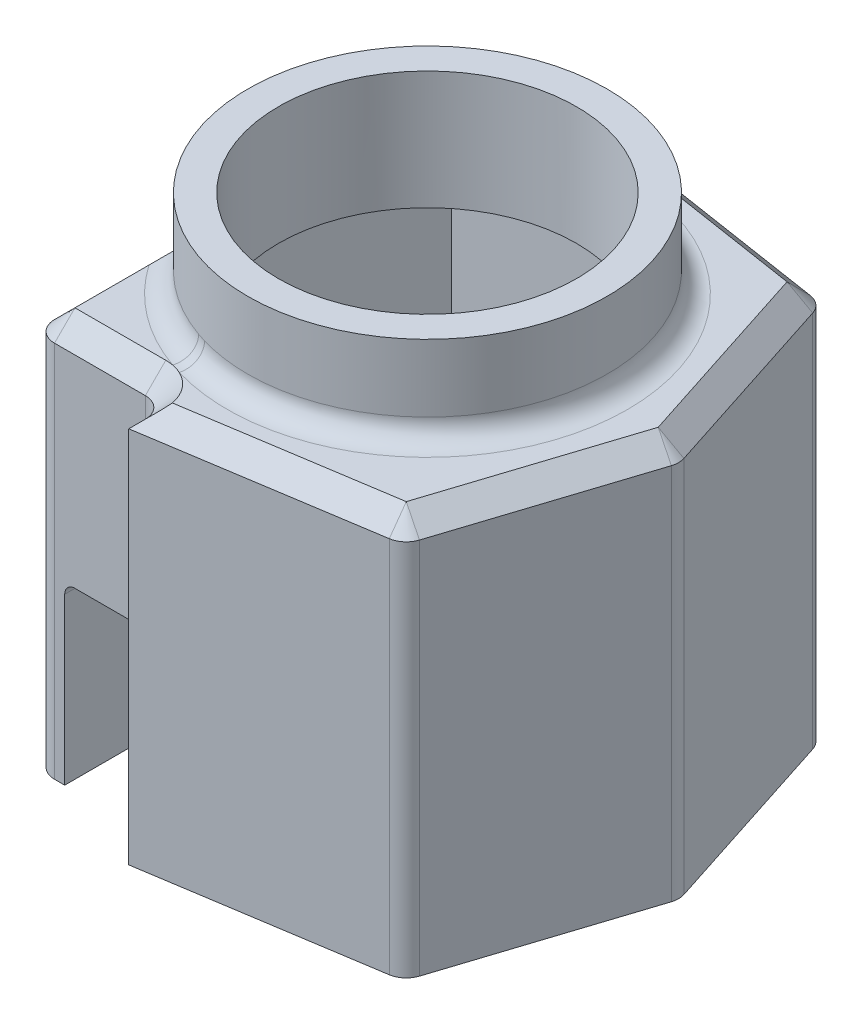
SolidWorks part; units mm, degrees
ref_plane "Front Plane" through (0, 0, 0) normal (0, 0, 1) x (1, 0, 0)
ref_plane "Top Plane" through (0, 0, 0) normal (0, 1, 0) x (1, 0, 0)
ref_plane "Right Plane" through (0, 0, 0) normal (1, 0, 0) x (0, 0, -1)
sketch "Sketch1" plane through (0, 0, 0) normal (0, 1, 0) x (1, 0, 0)
  line L1 (-14.9, -17.235) -> (14.9, -17.235)
  line L2 (-14.9, -17.235) -> (-14.9, 17.235)
  line L3 (-14.9, 17.235) -> (14.9, 17.235)
  line L4 (14.9, -17.235) -> (14.9, 17.235)
  line L5 (-14.9, -17.235) -> (14.9, 17.235) construction
  line L6 (-14.9, 17.235) -> (14.9, -17.235) construction
  point P0 (0, 0)
  dimension "D1" = 34.47
  dimension "D2" = 29.8
extrude "Boss-Extrude1" add sketch "Sketch1" along normal blind 33.8
sketch "Sketch2" plane through (0, 33.8, 0) normal (0, 1, 0) x (1, 0, 0)
  circle A0 centre (0, 0) radius 14.4
  dimension "D1" = 28.8
extrude "Boss-Extrude2" add sketch "Sketch2" along normal blind 11.8
sketch "Sketch3" plane through (0, 0, 17.235) normal (0, 0, 1) x (1, 0, 0)
  line L1 (-14.9, 0) -> (-5.4, 0)
  line L2 (-14.9, 0) -> (-14.9, 15)
  line L3 (-14.9, 15) -> (-5.4, 15)
  line L4 (-5.4, 0) -> (-5.4, 15)
  dimension "D1" = 15
  dimension "D2" = 9.5
extrude "Boss-Extrude3" add sketch "Sketch3" against normal offset from surface (54.47 mm away) 10 from offset 10 up to face at (0, 16.9, -17.235) offset beyond the face yes
sketch "Sketch4" plane through (0, 45.6, 0) normal (0, 1, 0) x (1, 0, 0)
  circle A1 centre (0, 0) radius 17.6
  circle A2 centre (0, 0) radius 14.6
  circle A3 centre (0, 0) radius 14.6
  dimension "D1" = 0.2
  dimension "D2" = 3
extrude "Boss-Extrude4" add sketch "Sketch4" against normal offset from surface (11.6 mm away) 0.2 separate body up to face at (0, 33.8, 14.4)
sketch "Sketch5" plane through (0, 34, 0) normal (0, -1, 0) x (1, 0, 0)
  line L4 (-18.1, -20.435) -> (18.1, -20.435)
  line L5 (18.1, -20.435) -> (18.1, 20.435)
  line L6 (18.1, 20.435) -> (-18.1, 20.435)
  line L7 (-18.1, 20.435) -> (-18.1, -20.435)
  line L8 (15.1, -17.435) -> (15.1, 17.435)
  line L9 (-15.1, -17.435) -> (15.1, -17.435)
  line L10 (-15.1, 17.435) -> (-15.1, -17.435)
  line L11 (15.1, 17.435) -> (-15.1, 17.435)
  line L12 (15.1, -17.435) -> (15.1, 17.435)
  line L13 (-15.1, -17.435) -> (15.1, -17.435)
  line L14 (-15.1, 17.435) -> (-15.1, -17.435)
  line L15 (15.1, 17.435) -> (-15.1, 17.435)
  dimension "D1" = 0.2
  dimension "D2" = 3
extrude "Boss-Extrude5" add sketch "Sketch5" along normal up to surface (34 mm away) up to face at (-2.7, 0, 0)
sketch "Sketch6" plane through (0, 0, 0) normal (0, -1, 0) x (1, 0, 0)
  line L16 (15.1, 17.435) -> (-5.2, 17.435)
  line L17 (-5.2, 17.435) -> (-5.2, 27.435)
  line L18 (-5.2, 27.435) -> (-15.1, 27.435)
  line L19 (-15.1, 27.435) -> (-15.1, -27.435)
  line L20 (-15.1, -27.435) -> (-5.2, -27.435)
  line L21 (-5.2, -27.435) -> (-5.2, -17.435)
  line L22 (-5.2, -17.435) -> (15.1, -17.435)
  line L23 (15.1, -17.435) -> (15.1, 17.435)
  line L24 (15.1, 17.435) -> (-5.2, 17.435)
  line L25 (-5.2, 17.435) -> (-5.2, 27.435)
  line L26 (-5.2, 27.435) -> (-15.1, 27.435)
  line L27 (-15.1, 27.435) -> (-15.1, -27.435)
  line L28 (-15.1, -27.435) -> (-5.2, -27.435)
  line L29 (-5.2, -27.435) -> (-5.2, -17.435)
  line L30 (-5.2, -17.435) -> (15.1, -17.435)
  line L31 (15.1, -17.435) -> (15.1, 17.435)
  dimension "D1" = 0.2
extrude "Cut-Extrude1" cut sketch "Sketch6" against normal offset from surface (15.2 mm away) 0.2 up to face at (-10.15, 15, 22.235) offset beyond the face yes
delete or keep bodies "Body-Delete/Keep 1" type delete bodies bodies 106
sketch "Sketch7" plane through (0, 34, 0) normal (0, -1, 0) x (1, 0, 0)
  line L16 (-18.1, 20.435) -> (-18.1, -20.435)
  line L17 (18.1, 20.435) -> (-18.1, 20.435)
  line L18 (18.1, -20.435) -> (18.1, 20.435)
  line L19 (-18.1, -20.435) -> (18.1, -20.435)
  line L20 (-18.1, 20.435) -> (-18.1, -20.435)
  line L21 (18.1, 20.435) -> (-18.1, 20.435)
  line L22 (18.1, -20.435) -> (18.1, 20.435)
  line L23 (-18.1, -20.435) -> (18.1, -20.435)
  circle A0 centre (0, 0) radius 14.6 construction
  circle A1 centre (0, 0) radius 14.6
  dimension "D1" = 0
extrude "Boss-Extrude6" add sketch "Sketch7" against normal blind 3
sketch "Sketch8" plane through (0, 37, 0) normal (0, 1, 0) x (1, 0, 0)
  line L0 (0, 0) -> (45.1825, 0) construction
  line L1 (18.1, 20.435) -> (24.7072, 0)
  line L2 (24.7072, 0) -> (18.1, -20.435)
  line L3 (18.1, -20.435) -> (18.1, 20.435)
  point P7 (22.4785, 0)
extrude "Boss-Extrude7" add sketch "Sketch8" against normal up to surface (37 mm away) up to face at (5.7, 0, 0)
sketch "Sketch9" plane through (0, 37, 0) normal (0, 1, 0) x (1, 0, 0)
  line L0 (-5.2, 20.435) -> (-5.2, 24.0622)
  line L1 (-5.2, 24.0622) -> (18.1, 20.435)
  line L2 (18.1, 20.435) -> (-5.2, 20.435)
  line L3 (0, 0) -> (41.759, 0) construction
  line L4 (18.1, -20.435) -> (-5.2, -20.435)
  line L5 (-5.2, -24.0622) -> (18.1, -20.435)
  line L6 (-5.2, -20.435) -> (-5.2, -24.0622)
  line M3 (18.1, 20.435) -> (-18.1, 20.435)
  line M5 (-18.1, -20.435) -> (18.1, -20.435)
extrude "Boss-Extrude8" add sketch "Sketch9" against normal up to surface (37 mm away) contours L1 L0 M3 | L6 L5 M5 region at (2.5667, 37, -21.6441) region at (2.5667, 37, 21.6441) up to face at (-16.6, 0, 0)
fillet "Fillet1" radius 2 7 edges at (-18.1, 18.5, 20.435) (-18.1, 18.5, -20.435) (18.1, 18.5, 20.435) (18.1, 18.5, -20.435) (24.7072, 18.5, 0) (-5.2, 26.1, 20.435) (-5.2, 26.1, -20.435)
fillet "Fillet2" radius 1 4 edges at (-15.1, 15.2, 18.935) (-5.2, 15.2, 19.935) (-15.1, 15.2, -18.935) (-5.2, 15.2, -19.935)
chamfer "Chamfer4" distance 2 angle 45 14 edges at (-5.7858, 37, 21.0208) (-5.7858, 37, -21.0208) (-11.65, 37, 20.435) (-11.65, 37, -20.435) (-17.5142, 37, 19.8492) (-17.5142, 37, -19.8492) (-18.1, 37, 0) (5.8417, 37, 22.3433) (17.8738, 37, 20.1698) (21.4935, 37, 9.9394) (24.6053, 37, 0) (21.4935, 37, -9.9394) (17.8738, 37, -20.1698) (5.8417, 37, -22.3433)
fillet "Fillet3" radius 2 1 edges at (17.6, 37, 0)
sketch "Sketch10" plane through (0, 0, 0) normal (0, -1, 0) x (1, 0, 0)
  line L0 (-15.1, 20.435) -> (-16.1, 20.435) construction
  line L1 (-18.1, 18.435) -> (-18.1, -18.435) construction
  line L2 (-16.1, -20.435) -> (-15.1, -20.435) construction
  line L3 (-15.1, -20.435) -> (-15.1, 20.435) construction
  line L4 (18.4788, -19.2635) -> (24.5083, -0.6153) construction
  line L5 (24.5083, 0.6153) -> (18.4788, 19.2635) construction
  line L6 (16.8834, 20.6244) -> (-5.2, 24.0622) construction
  line L7 (-5.2, 24.0622) -> (-5.2, 17.435) construction
  line L8 (-5.2, 17.435) -> (15.1, 17.435) construction
  line L9 (15.1, 17.435) -> (15.1, -17.435) construction
  line L10 (15.1, -17.435) -> (-5.2, -17.435) construction
  line L11 (-5.2, -17.435) -> (-5.2, -24.0622) construction
  line L12 (-5.2, -24.0622) -> (16.8834, -20.6244) construction
  line L13 (-15.1, 20.435) -> (-16.1, 20.435)
  line L14 (-18.1, 18.435) -> (-18.1, -18.435)
  line L15 (-16.1, -20.435) -> (-15.1, -20.435)
  line L16 (-15.1, -20.435) -> (-15.1, 20.435)
  line L17 (18.4788, -19.2635) -> (24.5083, -0.6153)
  line L18 (24.5083, 0.6153) -> (18.4788, 19.2635)
  line L19 (16.8834, 20.6244) -> (-5.2, 24.0622)
  line L20 (-5.2, 24.0622) -> (-5.2, 17.435)
  line L21 (-5.2, 17.435) -> (15.1, 17.435)
  line L22 (15.1, 17.435) -> (15.1, -17.435)
  line L23 (15.1, -17.435) -> (-5.2, -17.435)
  line L24 (-5.2, -17.435) -> (-5.2, -24.0622)
  line L25 (-5.2, -24.0622) -> (16.8834, -20.6244)
  arc A0 (-16.1, 20.435) -> (-18.1, 18.435) centre (-16.1, 18.435) ccw construction
  arc A1 (-18.1, -18.435) -> (-16.1, -20.435) centre (-16.1, -18.435) ccw construction
  arc A2 (24.5083, -0.6153) -> (24.5083, 0.6153) centre (22.6053, 0) ccw construction
  arc A3 (18.4788, 19.2635) -> (16.8834, 20.6244) centre (16.5758, 18.6482) ccw construction
  arc A4 (16.8834, -20.6244) -> (18.4788, -19.2635) centre (16.5758, -18.6482) ccw construction
  arc A5 (-16.1, 20.435) -> (-18.1, 18.435) centre (-16.1, 18.435) ccw
  arc A6 (-18.1, -18.435) -> (-16.1, -20.435) centre (-16.1, -18.435) ccw
  arc A7 (24.5083, -0.6153) -> (24.5083, 0.6153) centre (22.6053, 0) ccw
  arc A8 (18.4788, 19.2635) -> (16.8834, 20.6244) centre (16.5758, 18.6482) ccw
  arc A9 (16.8834, -20.6244) -> (18.4788, -19.2635) centre (16.5758, -18.6482) ccw
extrude "Boss-Extrude9" add sketch "Sketch10" along normal blind 2
